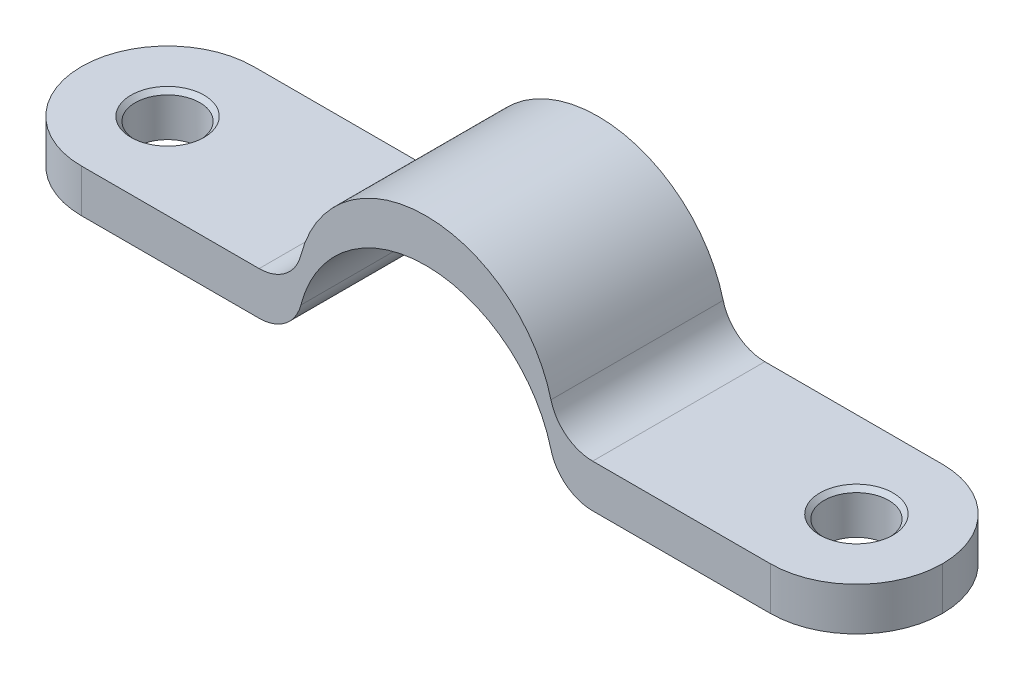
SolidWorks part; units mm, degrees
ref_plane "Front Plane" through (0, 0, 0) normal (0, 0, 1) x (1, 0, 0)
ref_plane "Top Plane" through (0, 0, 0) normal (0, 1, 0) x (1, 0, 0)
ref_plane "Right Plane" through (0, 0, 0) normal (1, 0, 0) x (0, 0, -1)
sketch "Sketch3" plane through (0, 0, 0) normal (0, 0, 1) x (1, 0, 0)
  line L0 (-38.7298, -5) -> (-100, -5)
  line L4 (-100, -5) -> (-100, 5)
  line L5 (38.7298, 5) -> (100, 5)
  line L6 (100, -5) -> (100, 5)
  line L7 (0, -37.1804) -> (0, 48.833) construction
  line L8 (38.7298, -5) -> (100, -5)
  line L9 (-38.7298, 5) -> (-100, 5)
  arc A2 (-29.0474, 2.5) -> (-38.7298, -5) centre (-38.7298, 5) cw
  arc A3 (-38.7298, 5) -> (-29.0474, 12.5) centre (-38.7298, 15) ccw
  arc A4 (29.0474, 12.5) -> (-29.0474, 12.5) centre (0, 5) ccw
  arc A5 (29.0474, 2.5) -> (-29.0474, 2.5) centre (0, -5) ccw
  arc A6 (38.7298, 5) -> (29.0474, 12.5) centre (38.7298, 15) cw
  arc A7 (29.0474, 2.5) -> (38.7298, -5) centre (38.7298, 5) ccw
  point P0 (0, 0)
  point P19 (28.2843, -5)
  point P20 (-28.2843, -5)
  dimension "D6" = 10
  dimension "D1" = 10
extrude "Boss-Extrude1" add sketch "Sketch3" along normal blind 40
fillet "Fillet1" radius 20 4 edges at (100, 0, 0) (100, 0, 40) (-100, 0, 0) (-100, 0, 40)
sketch "Sketch4" plane through (0, 5, 0) normal (0, 1, 0) x (1, 0, 0)
  circle A0 centre (80, -20) radius 7.5
  circle A2 centre (-80, -20) radius 7.5
  dimension "D1" = 15
  dimension "D2" = 15
extrude "Cut-Extrude1" cut sketch "Sketch4" against normal blind 40
chamfer "Chamfer1" distance 1 angle 45 2 edges at (72.5, 5, 20) (-87.5, 5, 20)
